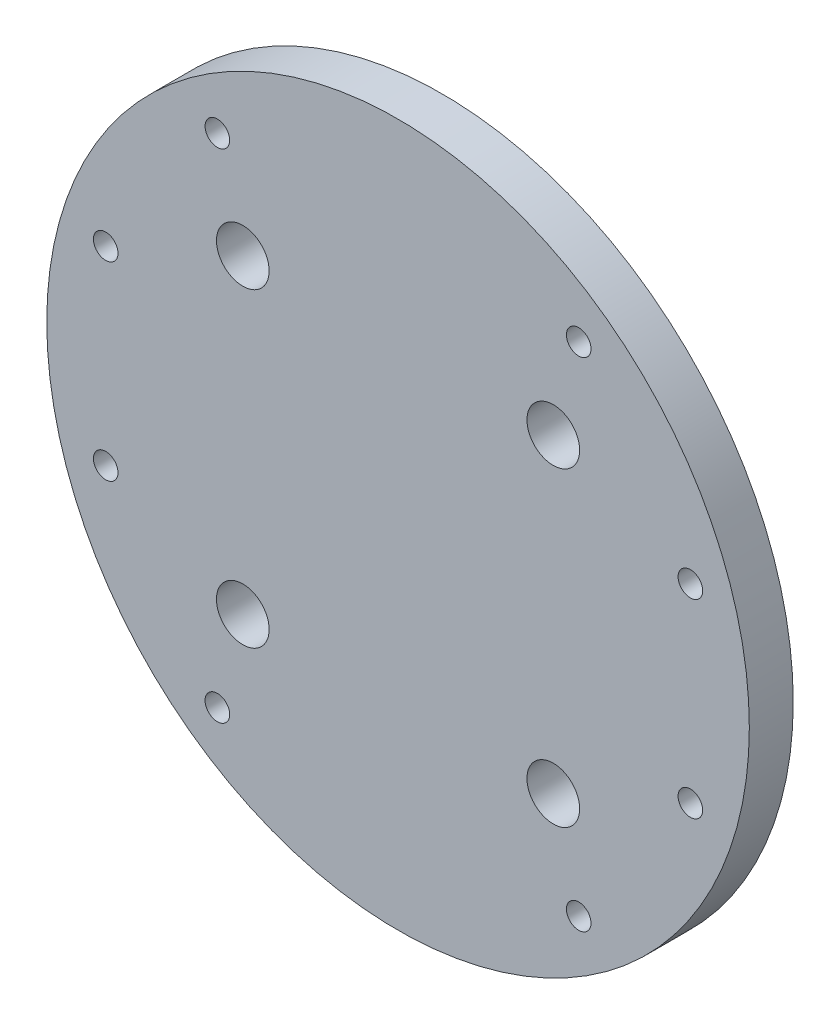
SolidWorks part; units mm, degrees
ref_plane "Front Plane" through (0, 0, 0) normal (0, 0, 1) x (1, 0, 0)
ref_plane "Top Plane" through (0, 0, 0) normal (0, 1, 0) x (1, 0, 0)
ref_plane "Right Plane" through (0, 0, 0) normal (1, 0, 0) x (0, 0, -1)
sketch "Sketch1" plane through (0, 0, 0) normal (0, 0, 1) x (1, 0, 0)
  circle A0 centre (0, 0) radius 40
  circle A6 centre (17.6777, 17.6777) radius 3
  circle A8 centre (17.6777, -17.6777) radius 3
  circle A10 centre (-17.6777, -17.6777) radius 3
  circle A12 centre (-17.6777, 17.6777) radius 3
  circle A31 centre (0, 0) radius 15.5
  circle A58 centre (20.5725, 28.3156) radius 1.4
  circle A59 centre (33.287, 10.8156) radius 1.4
  circle A60 centre (33.287, -10.8156) radius 1.4
  circle A61 centre (20.5725, -28.3156) radius 1.4
  circle A63 centre (-20.5725, -28.3156) radius 1.4
  circle A64 centre (-33.287, -10.8156) radius 1.4
  circle A65 centre (-33.287, 10.8156) radius 1.4
  circle A66 centre (-20.5725, 28.3156) radius 1.4
  circle A69 centre (20.5725, 28.3156) radius 2.75
  circle A70 centre (33.287, 10.8156) radius 2.75
  circle A71 centre (33.287, -10.8156) radius 2.75
  circle A72 centre (20.5725, -28.3156) radius 2.75
  circle A74 centre (-20.5725, -28.3156) radius 2.75
  circle A75 centre (-33.287, -10.8156) radius 2.75
  circle A76 centre (-33.287, 10.8156) radius 2.75
  circle A77 centre (-20.5725, 28.3156) radius 2.75
  point P27 (0, 0)
  point P36 (0, 0)
  point P37 (0, 0)
  point P38 (0, 0)
  point P45 (0, 0)
  point P54 (0, 0)
  point P58 (0, 0)
  point P65 (0, 0)
  dimension "D1" = 80
extrude "Boss-Extrude1" add sketch "Sketch1" along normal blind 5 contours A0
extrude "Cut-Extrude3" cut sketch "Sketch1<5>" along normal blind 5 contours A12 | A6 | A8 | A10 region at (17.6777, 17.6777, 0) region at (17.6777, -17.6777, 0) region at (-17.6777, -17.6777, 0) region at (-17.6777, 17.6777, 0)
sketch "Sketch1<5>" plane through (0, 0, 0) normal (0, 0, 1) x (1, 0, 0) same geometry as "Sketch1"
extrude "Boss-Extrude2" add sketch "Sketch1<8>" against normal blind 6 contours A31 region at (0, 0, 0)
sketch "Sketch1<8>" plane through (0, 0, 0) normal (0, 0, 1) x (1, 0, 0) same geometry as "Sketch1"
chamfer "Chamfer1" distance 1 angle 45 1 edges at (15.5, 0, -6)
extrude "Cut-Extrude12" cut sketch "Sketch1<20>" along normal blind 7 contours A66 | A58 | A59 | A60 | A61 | A63 | A64 | A65 region at (-20.5725, 28.3156, 0)
sketch "Sketch1<20>" plane through (0, 0, 0) normal (0, 0, 1) x (1, 0, 0) same geometry as "Sketch1"
extrude "Cut-Extrude13" cut sketch "Sketch1<22>" along normal blind 3 contours A77 | A76 | A75 | A74 | A72 | A71 | A70 | A69
sketch "Sketch1<22>" plane through (0, 0, 0) normal (0, 0, 1) x (1, 0, 0) same geometry as "Sketch1"
